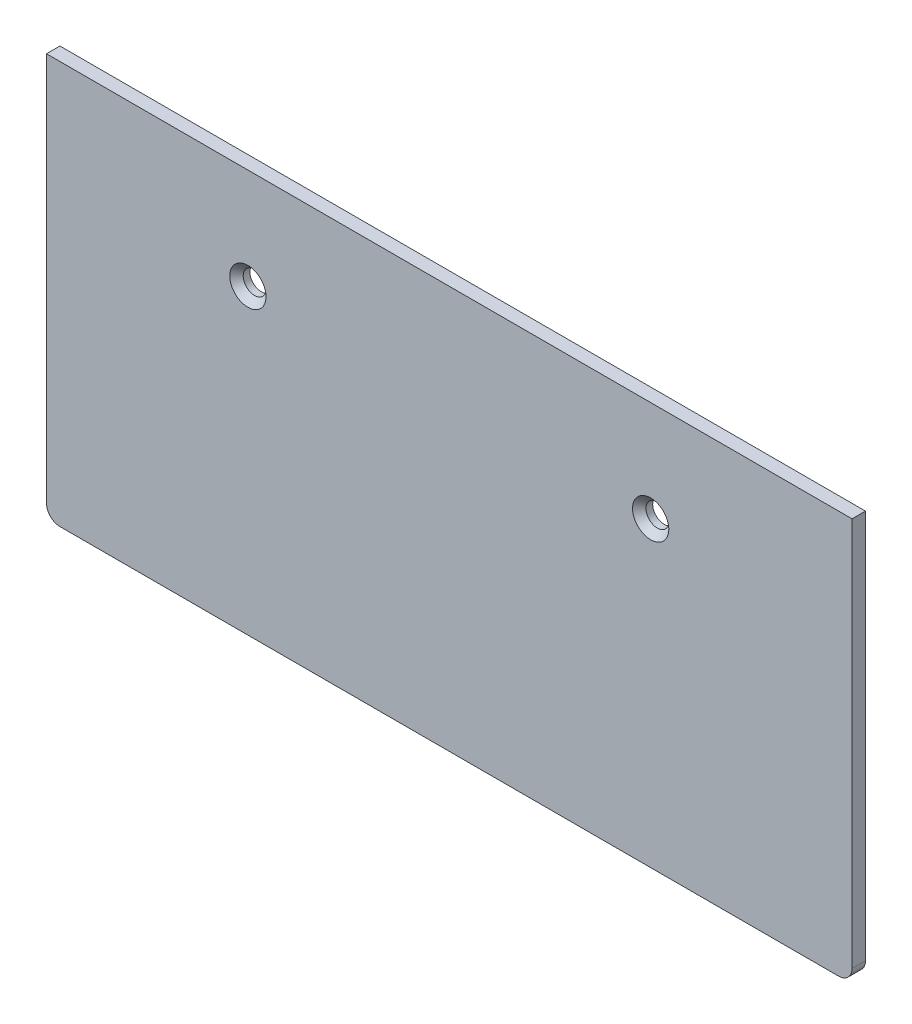
SolidWorks part; units mm, degrees
ref_plane "Piano frontale" through (0, 0, 0) normal (0, 0, 1) x (1, 0, 0)
ref_plane "Piano superiore" through (0, 0, 0) normal (0, 1, 0) x (1, 0, 0)
ref_plane "Piano destro" through (0, 0, 0) normal (1, 0, 0) x (0, 0, -1)
sketch "Schizzo1" plane through (0, 0, 0) normal (0, 0, 1) x (1, 0, 0)
  line L0 (60, 60) -> (60, 0) construction
  line L1 (0, 0) -> (120, 0)
  line L2 (0, 0) -> (0, 60)
  line L3 (0, 60) -> (120, 60)
  line L4 (120, 0) -> (120, 60)
  circle A0 centre (90, 45) radius 1.7
  circle A1 centre (30, 45) radius 1.7
  dimension "D5" = 3.4
  dimension "D1" = 60
  dimension "D2" = 120
  dimension "D3" = 30
  dimension "D4" = 15
extrude "Estrusione-Estrusione2" add sketch "Schizzo1" against normal blind 2
fillet "Raccordo1" radius 2 1 edges at (0, 0, -1) type face fillet first side face at (0, 30, -1) second side face at (60, 0, -1)
fillet "Raccordo2" radius 2 1 edges at (120, 0, -1) type face fillet first side face at (61, 0, -1) second side face at (120, 30, -1)
chamfer "Smusso1" distance 1 angle 45 1 edges at (28.3, 45, 0)
chamfer "Smusso2" distance 1 angle 45 1 edges at (91.7, 45, 0)
